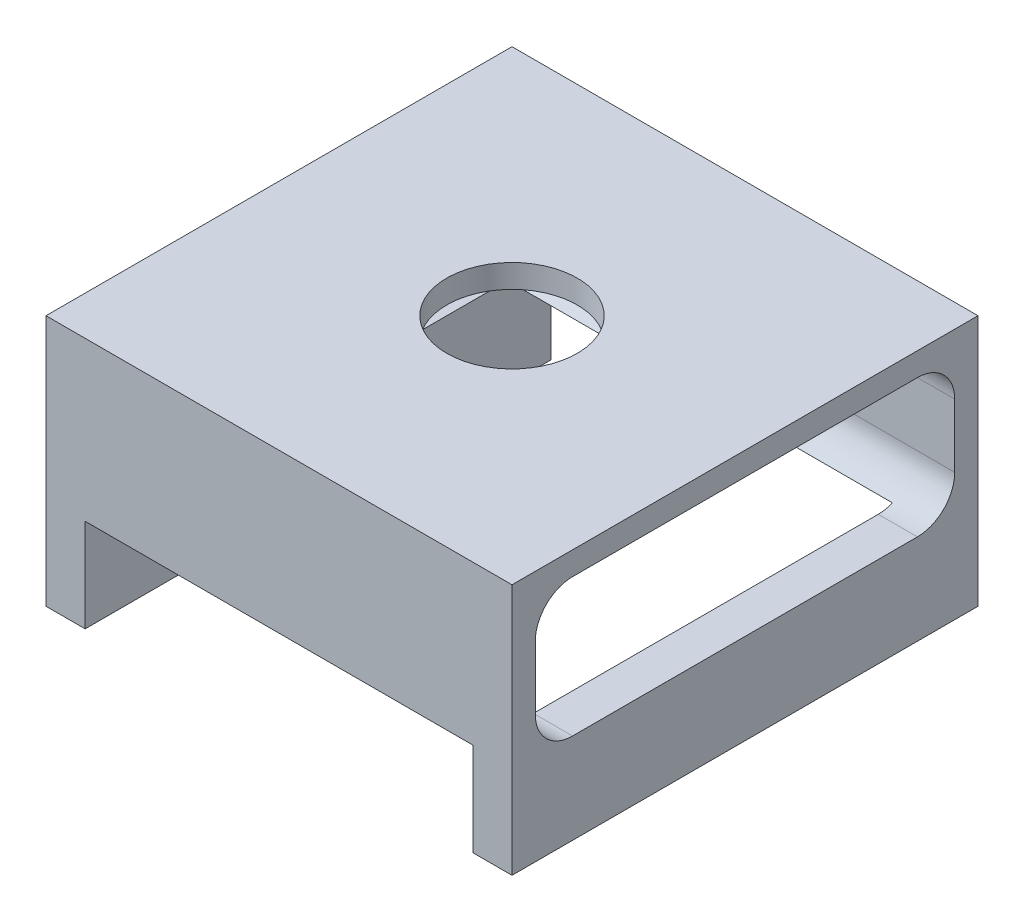
SolidWorks part; units mm, degrees
ref_plane "Front Plane" through (0, 0, 0) normal (0, 0, 1) x (1, 0, 0)
ref_plane "Top Plane" through (0, 0, 0) normal (0, 1, 0) x (1, 0, 0)
ref_plane "Right Plane" through (0, 0, 0) normal (1, 0, 0) x (0, 0, -1)
sketch "Sketch1" plane through (0, 0, 0) normal (0, 1, 0) x (1, 0, 0)
  line L1 (0, 0) -> (31.75, 0)
  line L2 (0, 0) -> (0, 31.75)
  line L3 (0, 31.75) -> (31.75, 31.75)
  line L4 (31.75, 0) -> (31.75, 31.75)
  dimension "D1" = 31.75
  dimension "D2" = 31.75
extrude "Boss-Extrude1" add sketch "Sketch1" along normal blind 17.145
sketch "Sketch2" plane through (0, 17.145, 0) normal (0, 1, 0) x (1, 0, 0)
  line L0 (31.75, 31.75) -> (0, 0) construction
  line L1 (31.75, 0) -> (0, 31.75) construction
  circle A0 centre (15.875, 15.875) radius 4.445
  dimension "D1" = 8.89
extrude "Cut-Extrude1" cut sketch "Sketch2" against normal through all
sketch "Sketch3" plane through (0, 0, 0) normal (0, 0, 1) x (1, 0, 0)
  line L0 (0, 0) -> (31.75, 0) construction
  line L1 (2.667, 0) -> (29.083, 0)
  line L2 (2.667, 0) -> (2.667, 6.35)
  line L3 (2.667, 6.35) -> (29.083, 6.35)
  line L4 (29.083, 0) -> (29.083, 6.35)
  line L5 (15.875, 17.145) -> (15.875, 0) construction
  line L6 (0, 17.145) -> (31.75, 17.145) construction
  point P10 (15.875, 6.35)
  dimension "D1" = 6.35
  dimension "D2" = 26.416
extrude "Cut-Extrude2" cut sketch "Sketch3" against normal through all
sketch "Sketch4" plane through (0, 0, 0) normal (-1, 0, 0) x (0, 0, 1)
  line L0 (-15.875, 17.145) -> (-15.875, 0) construction
  line L1 (-30.1625, 15.5575) -> (-1.5875, 15.5575)
  line L2 (-30.1625, 15.5575) -> (-30.1625, 6.1595)
  line L3 (-30.1625, 6.1595) -> (-1.5875, 6.1595)
  line L4 (-1.5875, 15.5575) -> (-1.5875, 6.1595)
  line L5 (-31.75, 17.145) -> (0, 17.145) construction
  line L6 (-31.75, 0) -> (0, 0) construction
  point P10 (-15.875, 15.5575)
  dimension "D1" = 28.575
  dimension "D2" = 9.398
  dimension "D3" = 1.5875
extrude "Cut-Extrude3" cut sketch "Sketch4" against normal through all
fillet "Fillet2" radius 2.54 4 edges at (30.4165, 6.1595, -30.1625) (1.3335, 6.1595, -1.5875) (15.875, 15.5575, -1.5875) (15.875, 15.5575, -30.1625)
